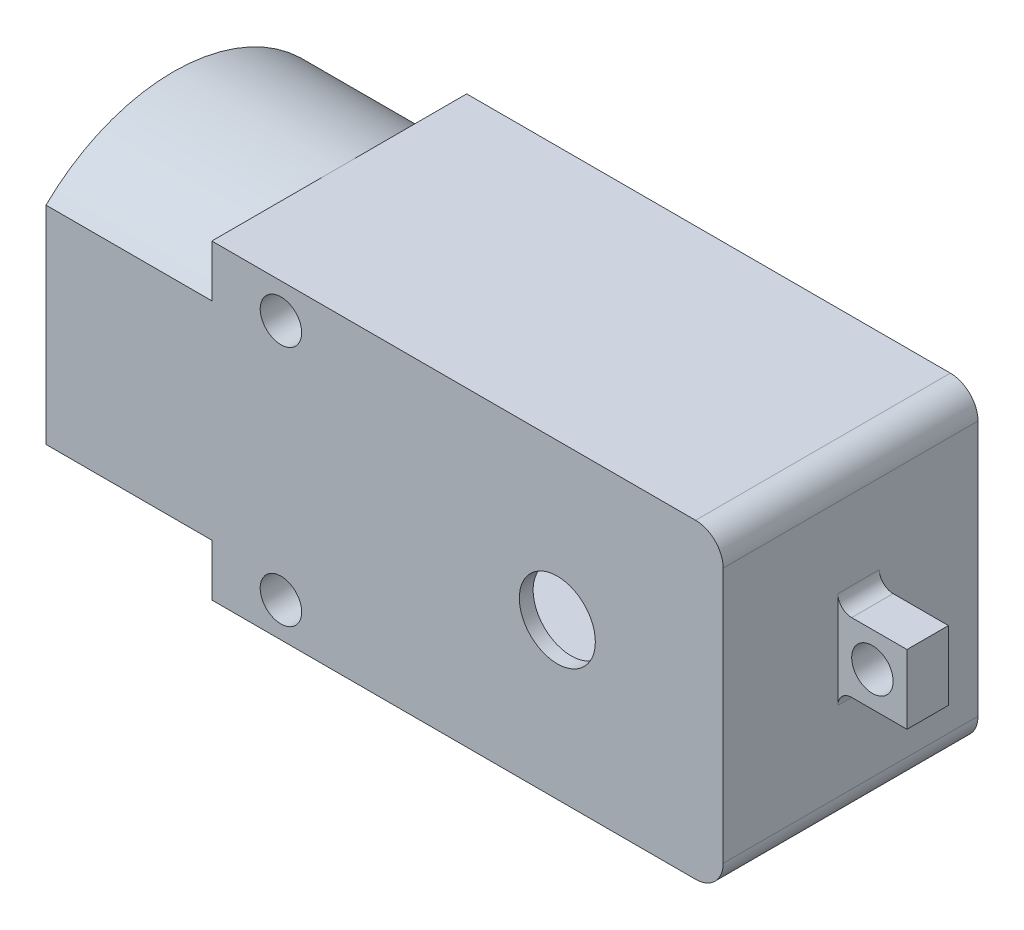
SolidWorks part; units mm, degrees
ref_plane "Front Plane" through (0, 0, 0) normal (0, 0, 1) x (1, 0, 0)
ref_plane "Top Plane" through (0, 0, 0) normal (0, 1, 0) x (1, 0, 0)
ref_plane "Right Plane" through (0, 0, 0) normal (1, 0, 0) x (0, 0, -1)
sketch "Sketch1" plane through (0, 0, 0) normal (0, 0, 1) x (1, 0, 0)
  line L1 (17.5, -11.25) -> (-17.5, -11.25)
  line L2 (19.5, -9.25) -> (19.5, 9.25)
  line L3 (17.5, 11.25) -> (-17.5, 11.25)
  line L4 (-17.5, -11.25) -> (-17.5, 11.25)
  line L5 (0, 11.25) -> (0, -11.25) construction
  line L6 (19.5, 0) -> (-17.5, 0) construction
  arc A0 (17.5, -11.25) -> (19.5, -9.25) centre (17.5, -9.25) ccw
  arc A1 (19.5, 9.25) -> (17.5, 11.25) centre (17.5, 9.25) ccw
  circle A2 centre (-12.5, 8.75) radius 1.5
  circle A3 centre (-12.5, -8.75) radius 1.5
  point P0 (0, 0)
  dimension "D1" = 2
  dimension "D4" = 3
  dimension "D6" = 17.5
  dimension "D2" = 22.5
  dimension "D3" = 37
  dimension "D5" = 5
extrude "Boss-Extrude1" add sketch "Sketch1" along normal mid plane 18.44
ref_plane "Plane1" through (0, 0, -0.58) normal (0, 0, 1) x (1, 0, 0)
sketch "Sketch2" plane through (-17.5, 0, 0) normal (-1, 0, 0) x (0, 0, 1)
  line L0 (9.22, -7.5) -> (9.22, 7.5)
  line L1 (-9.22, 11.25) -> (-9.22, -11.25) construction
  line L2 (9.22, 11.25) -> (9.22, -11.25) construction
  line L3 (0, 11.25) -> (0, -11.25) construction
  line L4 (9.22, 11.25) -> (-9.22, 11.25) construction
  line L5 (9.22, -11.25) -> (-9.22, -11.25) construction
  line L6 (-9.22, 0) -> (9.22, 0) construction
  line L7 (-9.22, -7.5) -> (-9.22, 7.5)
  arc A0 (9.22, 7.5) -> (-9.22, 7.5) centre (0, -1.9595) ccw
  arc A1 (9.22, -7.5) -> (-9.22, -7.5) centre (0, 1.9595) cw
  point P5 (9.22, 0)
  point P14 (0, 0)
  dimension "D1" = 15
extrude "Boss-Extrude2" add sketch "Sketch2" along normal blind 12
shell "Shell1" thickness 1 removed face at (-29.5, 0, 0)
sketch "Sketch3" plane through (-17.5, 0, 0) normal (-1, 0, 0) x (0, 0, 1)
  line L2 (-9.22, 7.5) -> (-9.22, -7.5)
  line L3 (9.22, -7.5) -> (9.22, 7.5)
  line L4 (-9.22, 7.5) -> (-9.22, -7.5)
  line L5 (9.22, -7.5) -> (9.22, 7.5)
  circle A0 centre (0, 0) radius 1.5
  arc A2 (9.22, 7.5) -> (-9.22, 7.5) centre (0, -1.9595) ccw
  arc A3 (-9.22, -7.5) -> (9.22, -7.5) centre (0, 1.9595) ccw
  arc A4 (9.22, 7.5) -> (-9.22, 7.5) centre (0, -1.9595) ccw
  arc A5 (-9.22, -7.5) -> (9.22, -7.5) centre (0, 1.9595) ccw
  dimension "D2" = 3
  dimension "D1" = 0
extrude "Boss-Extrude3" add sketch "Sketch3" along normal blind 1
sketch "Sketch6" plane through (0, 0, -0.58) normal (0, 0, 1) x (1, 0, 0)
  line L0 (19.5, 2.5) -> (24.5, 2.5)
  line L1 (19.5, -9.25) -> (19.5, 9.25) construction
  line L2 (24.5, 2.5) -> (24.5, -2.5)
  line L3 (24.5, -2.5) -> (19.5, -2.5)
  line L4 (24.5, 0) -> (-29.5, 0) construction
  line L5 (-29.5, 7.5) -> (-29.5, -7.5) construction
  line L6 (19.5, 2.5) -> (19.5, -2.5)
  line L7 (22, -2.5) -> (22, 2.5) construction
  circle A0 centre (22, 0) radius 1.5
  dimension "D3" = 3
  dimension "D1" = 5
  dimension "D2" = 5
extrude "Boss-Extrude4" add sketch "Sketch6" against normal blind 1.5 and the other way blind 1.5
sketch "Sketch7" plane through (0, 0, 9.22) normal (0, 0, 1) x (1, 0, 0)
  line L0 (-29.5, 0) -> (24.5, 0) construction
  line L1 (-29.5, -7.5) -> (-29.5, 7.5) construction
  line L2 (24.5, -2.5) -> (24.5, 2.5) construction
  circle A0 centre (7.5, 0) radius 2.75
  circle A1 centre (-12.5, 8.75) radius 1.5 construction
  circle A2 centre (22, 0) radius 1.5 construction
  dimension "D1" = 20
  dimension "D2" = 5.5
  dimension "D3" = 14.5
extrude "Cut-Extrude1" cut sketch "Sketch7" against normal through all
fillet "Fillet1" radius 1 2 edges at (19.5, -2.5, -0.58) (19.5, 2.5, -0.58)
